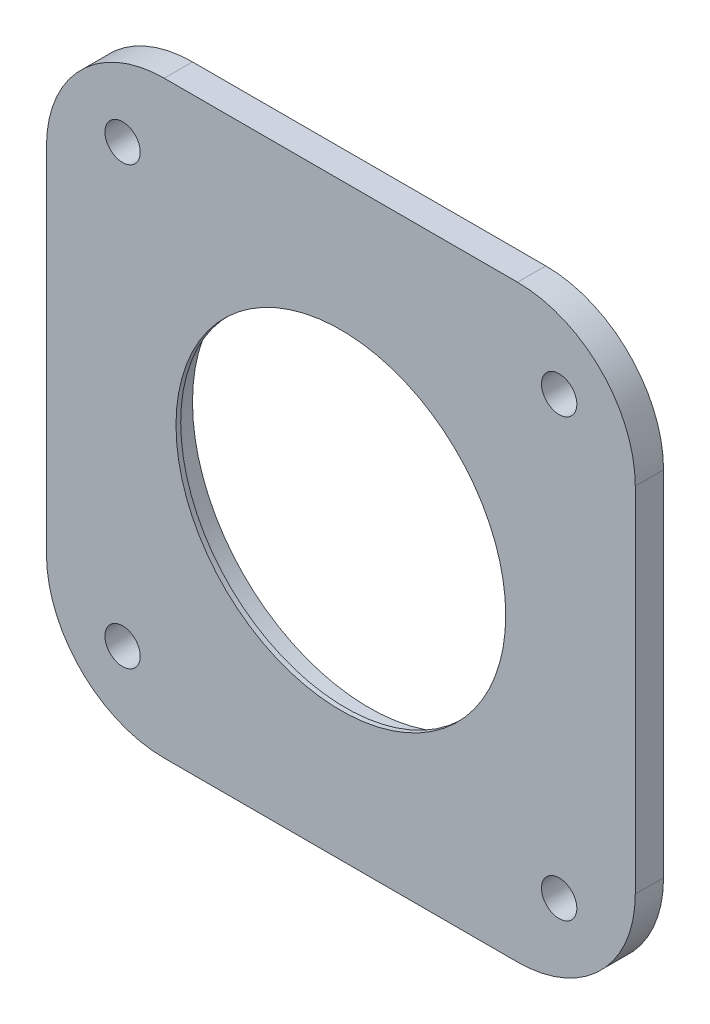
SolidWorks part; units mm, degrees
ref_plane "Front Plane" through (0, 0, 0) normal (0, 0, 1) x (1, 0, 0)
ref_plane "Top Plane" through (0, 0, 0) normal (0, 1, 0) x (1, 0, 0)
ref_plane "Right Plane" through (0, 0, 0) normal (1, 0, 0) x (0, 0, -1)
sketch "Sketch1" plane through (0, 0, 0) normal (0, 0, 1) x (1, 0, 0)
  line L7 (-19.05, -31.75) -> (19.05, -31.75)
  line L8 (-31.75, -19.05) -> (-31.75, 19.05)
  line L9 (-19.05, 31.75) -> (19.05, 31.75)
  line L10 (31.75, -19.05) -> (31.75, 19.05)
  line L11 (-31.75, -31.75) -> (31.75, 31.75) construction
  line L12 (-31.75, 31.75) -> (31.75, -31.75) construction
  circle A0 centre (0, 0) radius 19.05
  arc A1 (-19.05, -31.75) -> (-31.75, -19.05) centre (-19.05, -19.05) cw
  arc A2 (19.05, -31.75) -> (31.75, -19.05) centre (19.05, -19.05) ccw
  arc A3 (19.05, 31.75) -> (31.75, 19.05) centre (19.05, 19.05) cw
  arc A4 (-31.75, 19.05) -> (-19.05, 31.75) centre (-19.05, 19.05) cw
  circle A5 centre (-23.5401, 23.5401) radius 1.905
  circle A6 centre (23.5401, 23.5401) radius 1.905
  circle A7 centre (23.5401, -23.5401) radius 1.905
  circle A8 centre (-23.5401, -23.5401) radius 1.905
  point P21 (-28.0303, 28.0303)
  point P31 (0, 0)
  dimension "D1" = 12.7
  dimension "D2" = 38.1
  dimension "D3" = 6.35
  dimension "D4" = 4
extrude "Boss-Extrude1" add sketch "Sketch1" along normal blind 3.048
sketch "Sketch2" plane through (0, 0, 3.048) normal (0, 0, 1) x (1, 0, 0)
  circle A0 centre (0, 0) radius 19.05
  circle A1 centre (0, 0) radius 17.78
extrude "Boss-Extrude2" add sketch "Sketch2" against normal blind 0.508
